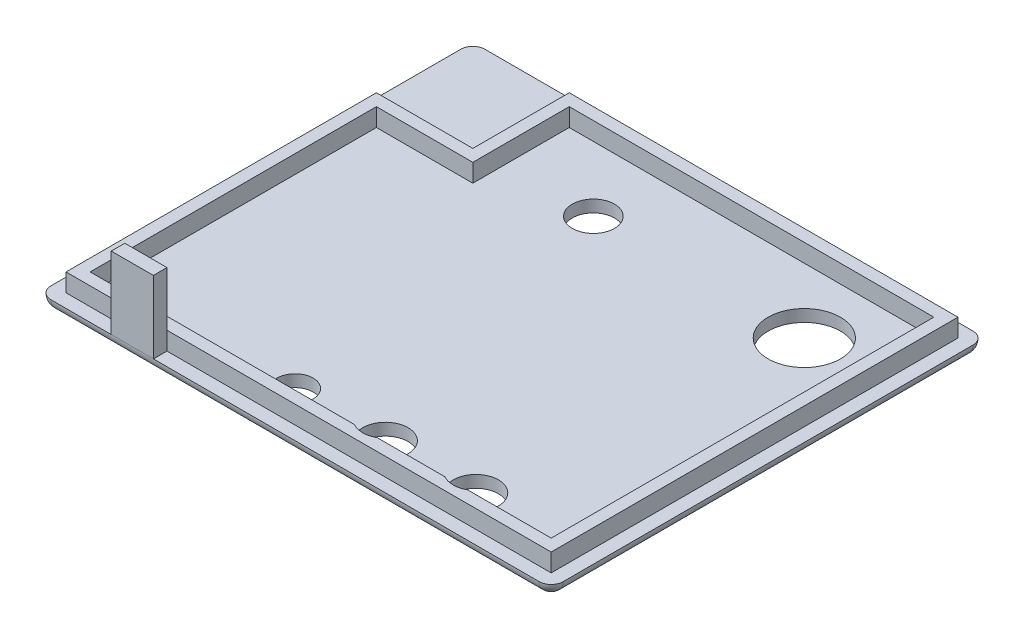
SolidWorks part; units mm, degrees
ref_plane "Plan de face" through (0, 0, 0) normal (0, 0, 1) x (1, 0, 0)
ref_plane "Plan de dessus" through (0, 0, 0) normal (0, 1, 0) x (1, 0, 0)
ref_plane "Plan de droite" through (0, 0, 0) normal (1, 0, 0) x (0, 0, -1)
sketch "Esquisse1" plane through (0, 0, 0) normal (0, 1, 0) x (1, 0, 0)
  line L0 (0, 36) -> (0, -36) construction
  line L1 (-42.5, 36) -> (42.5, 36)
  line L2 (-42.5, 36) -> (-42.5, -36)
  line L3 (-42.5, -36) -> (42.5, -36)
  line L4 (42.5, 36) -> (42.5, -36)
  dimension "D1" = 85
  dimension "D2" = 72
extrude "Boss.-Extru.1" add sketch "Esquisse1" along normal blind 2
sketch "Esquisse2" plane through (0, 2, 0) normal (0, 1, 0) x (1, 0, 0)
  line L0 (40.25, -33.75) -> (-40.25, -33.75)
  line L4 (-24.25, 33.75) -> (40.25, 33.75)
  line L5 (40.25, 33.75) -> (40.25, -33.75)
  line L6 (42.5, 36) -> (-42.5, 36) construction
  line L7 (-42.5, 36) -> (-42.5, -36) construction
  line L8 (42.5, -36) -> (42.5, 36) construction
  line L9 (-42.5, -36) -> (42.5, -36) construction
  line L13 (-38.25, -31.75) -> (38.25, -31.75)
  line L14 (38.25, -31.75) -> (38.25, 31.75)
  line L15 (38.25, 31.75) -> (-22.25, 31.75)
  line L16 (-22.25, 31.75) -> (-22.25, 15.75)
  line L17 (-22.25, 15.75) -> (-38.25, 15.75)
  line L18 (-38.25, 15.75) -> (-38.25, -31.75)
  line L20 (-24.25, 33.75) -> (-24.25, 17.75)
  line L21 (-24.25, 17.75) -> (-40.25, 17.75)
  line L22 (-40.25, 17.75) -> (-40.25, -33.75)
  point P2 (-25.8142, -31.5)
  point P18 (0, 0)
  dimension "D1" = 2.25
  dimension "D2" = 2
  dimension "D3" = 2.25
  dimension "D4" = 2.25
  dimension "D5" = 2
  dimension "D6" = 16
  dimension "D7" = 2
  dimension "D8" = 2
  dimension "D9" = 2
  dimension "D10" = 2
  dimension "D11" = 2.25
  dimension "D12" = 16
extrude "Boss.-Extru.2" add sketch "Esquisse2" along normal blind 3
sketch "Esquisse3" plane through (0, 0, 0) normal (0, -1, 0) x (-1, 0, 0)
  line L0 (42.5, -28.5) -> (-42.5, -28.5) construction
  line L1 (42.5, 36) -> (42.5, -36) construction
  line L2 (-42.5, -36) -> (-42.5, 36) construction
  line L3 (42.5, -36) -> (-42.5, -36) construction
  circle A6 centre (-22.5, -28.5) radius 3.75
  circle A7 centre (-7.5, -28.5) radius 3.75
  circle A8 centre (7.5, -28.5) radius 3
  dimension "D1" = 7.5
  dimension "D2" = 6
  dimension "D3" = 7.5
  dimension "D4" = 7.5
  dimension "D5" = 15
  dimension "D6" = 15
  dimension "D7" = 20
extrude "Enlèv. mat.-Extru.1" cut sketch "Esquisse3" against normal through all
sketch "Esquisse4" plane through (0, 0, 0) normal (0, -1, 0) x (-1, 0, 0)
  line L0 (-42.5, -36) -> (-42.5, 36) construction
  line L1 (-42.5, 36) -> (42.5, 36) construction
  line L2 (42.5, 36) -> (42.5, -36) construction
  circle A0 centre (-27.5, 21) radius 6
  circle A1 centre (7.5, 21) radius 3.5
  dimension "D1" = 12
  dimension "D4" = 7
  dimension "D2" = 15
  dimension "D3" = 15
  dimension "D5" = 35
  dimension "D6" = 15
extrude "Enlèv. mat.-Extru.2" cut sketch "Esquisse4" against normal blind 2
sketch "Esquisse8" plane through (0, 2, 0) normal (0, 1, 0) x (1, 0, 0)
  line L0 (-40.25, -33.75) -> (40.25, -33.75) construction
  line L1 (-30.5, -33.75) -> (-23.5, -33.75)
  line L2 (-30.5, -33.75) -> (-30.5, -36)
  line L3 (-30.5, -36) -> (-23.5, -36)
  line L4 (-23.5, -33.75) -> (-23.5, -36)
  line L5 (-42.5, -36) -> (42.5, -36) construction
  line L6 (-42.5, 36) -> (-42.5, -36) construction
  dimension "D1" = 7
  dimension "D2" = 12
extrude "Boss.-Extru.4" add sketch "Esquisse8" along normal blind 12
fillet "Congé4" radius 2 4 edges at (0, 0, 36) (-42.5, 0, 0) (0, 0, -36) (42.5, 0, 0)
